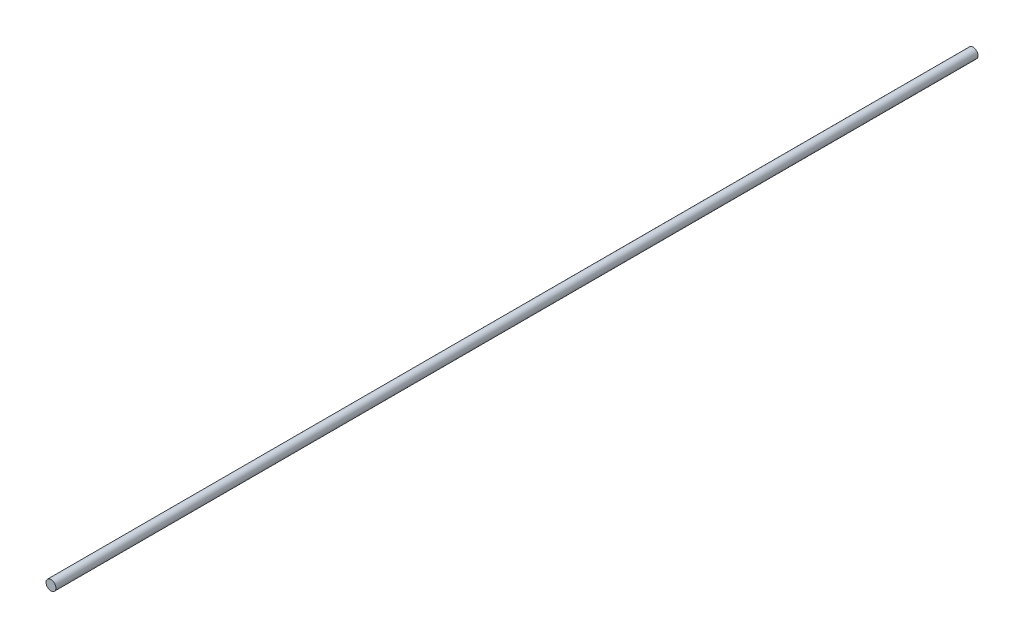
SolidWorks part; units mm, degrees
material "AISI 1020"
ref_plane "Front Plane" through (0, 0, 0) normal (0, 0, 1) x (1, 0, 0)
ref_plane "Top Plane" through (0, 0, 0) normal (0, 1, 0) x (1, 0, 0)
ref_plane "Right Plane" through (0, 0, 0) normal (1, 0, 0) x (0, 0, -1)
sketch "Sketch1" plane through (0, 0, 0) normal (0, 0, 1) x (1, 0, 0)
  circle A0 centre (0, 0) radius 7.9375
  dimension "D1" = 15.875
extrude "Boss-Extrude1" add sketch "Sketch1" along normal blind 2254.25
sketch "Sketch2" plane through (0, 0, 0) normal (0, 0, -1) x (-1, 0, 0)
  circle A0 centre (0, 0) radius 7.9375
extrude "Cut-Extrude1" cut sketch "Sketch2" against normal blind 520.7
sketch "Sketch3" plane through (0, 0, 2254.25) normal (0, 0, 1) x (1, 0, 0)
  circle A0 centre (0, 0) radius 7.9375
extrude "Cut-Extrude2" cut sketch "Sketch3" against normal blind 254
